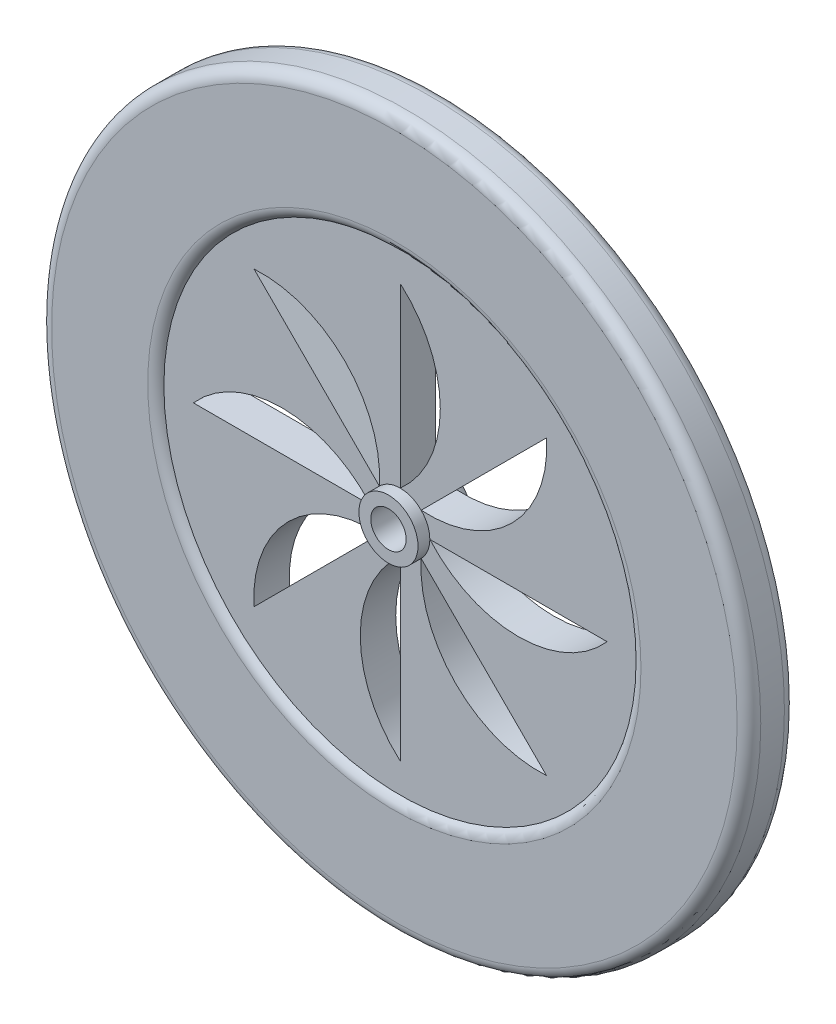
SolidWorks part; units mm, degrees
ref_plane "Front Plane" through (0, 0, 0) normal (0, 0, 1) x (1, 0, 0)
ref_plane "Top Plane" through (0, 0, 0) normal (0, 1, 0) x (1, 0, 0)
ref_plane "Right Plane" through (0, 0, 0) normal (1, 0, 0) x (0, 0, -1)
sketch "Sketch1" plane through (0, 0, 0) normal (0, 0, 1) x (1, 0, 0)
  circle A0 centre (0, 0) radius 2.5
  dimension "D1" = 5
extrude "Boss-Extrude5" add sketch "Sketch1" along normal mid plane 5 contours A0
sketch "Sketch7" plane through (0, 0, 0) normal (0, 0, 1) x (1, 0, 0)
  circle A0 centre (0, 0) radius 20
  dimension "D1" = 40
extrude "Boss-Extrude6" add sketch "Sketch7" along normal mid plane 3
sketch "Sketch8" plane through (0, 0, 1.5) normal (0, 0, 1) x (1, 0, 0)
  line L0 (0, 2.5) -> (0, 17.5)
  line L1 (1.7678, 1.7678) -> (12.3744, 12.3744)
  line L2 (2.5, 0) -> (17.5, 0)
  line L3 (1.7678, -1.7678) -> (12.3744, -12.3744)
  line L4 (0, -2.5) -> (0, -17.5)
  line L5 (-1.7678, -1.7678) -> (-12.3744, -12.3744)
  line L6 (-2.5, 0) -> (-17.5, 0)
  line L7 (-1.7678, 1.7678) -> (-12.3744, 12.3744)
  circle A0 centre (0, 0) radius 2.5 construction
  circle A1 centre (0, 0) radius 2.5 construction
  arc A2 (0, 17.5) -> (0, 2.5) centre (-6.6144, 10) cw
  arc A3 (12.3744, 12.3744) -> (1.7678, 1.7678) centre (2.394, 11.7481) cw
  arc A4 (17.5, 0) -> (2.5, 0) centre (10, 6.6144) cw
  arc A5 (12.3744, -12.3744) -> (1.7678, -1.7678) centre (11.7481, -2.394) cw
  arc A6 (0, -17.5) -> (0, -2.5) centre (6.6144, -10) cw
  arc A7 (-12.3744, -12.3744) -> (-1.7678, -1.7678) centre (-2.394, -11.7481) cw
  arc A8 (-17.5, 0) -> (-2.5, 0) centre (-10, -6.6144) cw
  arc A9 (-12.3744, 12.3744) -> (-1.7678, 1.7678) centre (-11.7481, 2.394) cw
  point P32 (0, 0)
  dimension "D1" = 10
  dimension "D3" = 15
  dimension "D2" = 8
extrude "Cut-Extrude5" cut sketch "Sketch8" against normal blind 3
sketch "Sketch9" plane through (0, 0, 0) normal (0, 0, 1) x (1, 0, 0)
  circle A0 centre (0, 0) radius 30
  circle A1 centre (0, 0) radius 20
  dimension "D1" = 60
  dimension "D2" = 40
extrude "Boss-Extrude8" add sketch "Sketch9" along normal mid plane 4
sketch "Sketch10" plane through (0, 0, 2.5) normal (0, 0, 1) x (1, 0, 0)
  circle A0 centre (0, 0) radius 1.5
extrude "Cut-Extrude6" cut sketch "Sketch10" against normal blind 2
sketch "Sketch11" plane through (0, 0, 0.5) normal (0, 0, 1) x (1, 0, 0)
  line L0 (-1.5, 0) -> (1.5, 0)
  circle A0 centre (0, 0) radius 1.5 construction
  arc A1 (-1.5, 0) -> (1.5, 0) centre (0, 0) ccw
extrude "Cut-Extrude7" cut sketch "Sketch11" against normal blind 2
fillet "Fillet1" radius 1 1 edges at (2.5, 0, -2.5)
fillet "Fillet2" radius 1 4 edges at (20, 0, 2) (20, 0, -2) (30, 0, -2) (30, 0, 2)
